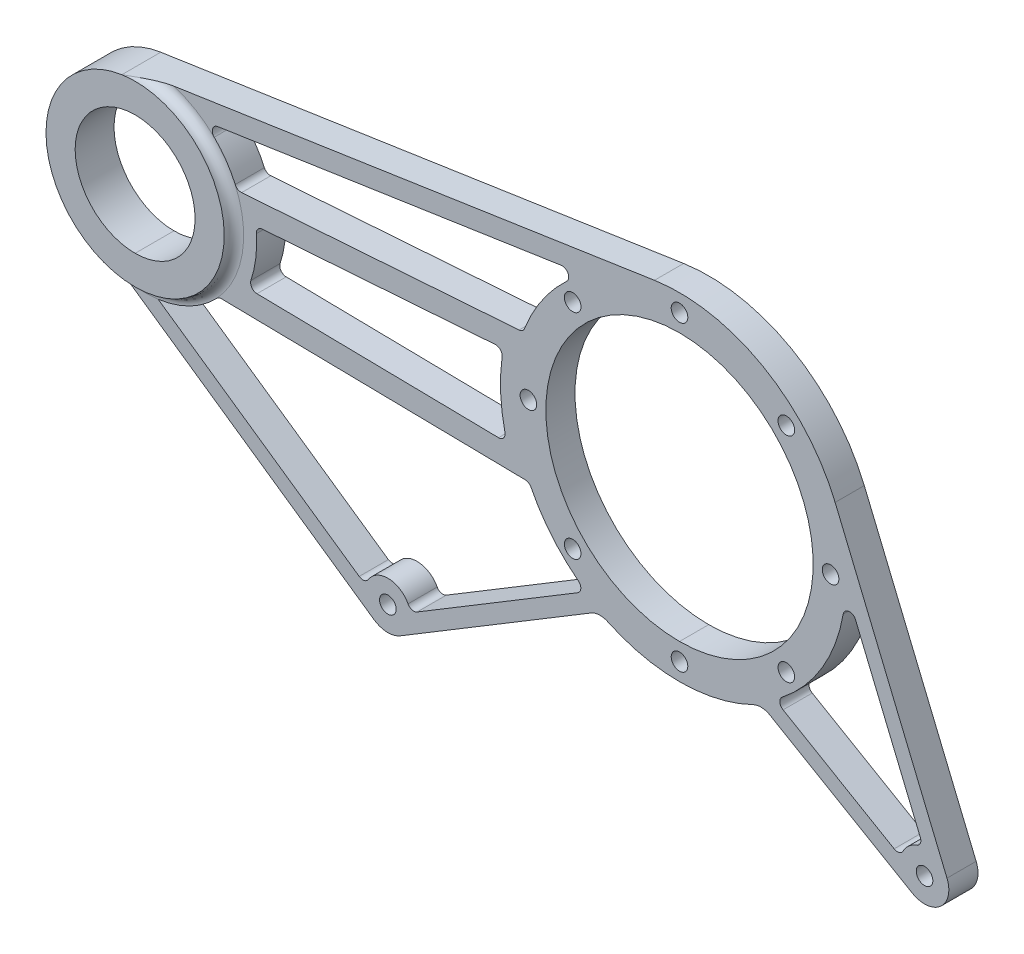
SolidWorks part; units mm, degrees
note: '?' marks a value the reader was unsure of.
material "6061-T6 (SS)"
ref_plane "Front Plane" through (0, 0, 0) normal (0, 0, 1) x (1, 0, 0)
ref_plane "Top Plane" through (0, 0, 0) normal (0, 1, 0) x (1, 0, 0)
ref_plane "Right Plane" through (0, 0, 0) normal (1, 0, 0) x (0, 0, -1)
sketch "Sketch1" plane through (0, 0, 0) normal (0, 0, 1) x (1, 0, 0)
  line L0 (-329.0358, 136.1378) -> (-124.1059, 166.9079)
  line L1 (-343.7594, 72.9056) -> (-234.0298, -3.2296)
  line L2 (-223.6766, -3.5577) -> (-149.0272, 41.5159)
  line L3 (-114.3, 88.9) -> (-114.3, 101.6) construction
  line L4 (-53.3056, 126.9173) -> (-9.4675, 21.3025)
  line L5 (-23.0618, 9.4221) -> (-78.8665, 41.9532)
  circle A0 centre (-114.3, 88.9) radius 82.9716 construction
  circle A1 centre (-228.6, -20.8038) radius 12.7 construction
  circle A2 centre (0, 0) radius 12.7 construction
  circle A3 centre (-323.85, 101.6) radius 114 construction
  circle A4 centre (-323.85, 101.6) radius 23.5
  circle A5 centre (-114.3, 101.6) radius 52.3875
  arc A6 (-142.4404, 41.8555) -> (-85.4371, 42.2012) centre (-114.3, 101.6) ccw
  circle A7 centre (-323.85, 101.6) radius 34.925
  arc A8 (-223.6766, -3.5577) -> (-234.0298, -3.2296) centre (-228.6, 4.5962) cw
  arc A9 (-9.4675, 21.3025) -> (-23.0618, 9.4221) centre (-18.2648, 17.651) cw
  circle A10 centre (-228.6, 4.5962) radius 3.2512
  circle A11 centre (-18.2648, 17.651) radius 3.2512
  arc A12 (-142.4404, 41.8555) -> (-149.0272, 41.5159) centre (-145.4168, 35.5364) ccw
  arc A13 (-78.8665, 41.9532) -> (-85.4371, 42.2012) centre (-82.3843, 35.9187) ccw
  circle A14 centre (-114.3, 101.6) radius 66.04 construction
  arc A15 (-124.1059, 166.9079) -> (-53.3056, 126.9173) centre (-114.3, 101.6) cw
  dimension "D1" = 88.9
  dimension "D2" = 12.7
  dimension "D3" = 25.4
  dimension "D4" = 25.4
  dimension "D8" = 165.9433
  dimension "D9" = 228
  dimension "D10" = 47
  dimension "D12" = 104.775
  dimension "D14" = 132.08
  dimension "D15" = 69.85
  dimension "D16" = 9.525
  dimension "D18" = 9.525
  dimension "D20" = 6.5024
  dimension "D21" = 6.5024
  dimension "D23" = 6.985
  dimension "D24" = 6.985
  dimension "D25" = 66.04
  dimension "D5" = 228.6
  dimension "D6" = 20.8038
  dimension "D7" = 114.3
  dimension "D11" = 12.7
  dimension "D13" = 209.55
  dimension "D17" = 25.4
  dimension "D19" = 25.4
  dimension "D22" = 17.651
extrude "Boss-Extrude1" add sketch "Sketch1" along normal blind 11.43 contours A7 A4 | A8 L2 A6 L0 A7 L1 A10 | A6 A5 | A9 L4 A6 L5 A11
ref_point "Point4"
sketch "Sketch5" plane through (0, 0, 11.43) normal (0, 0, 1) x (1, 0, 0)
  circle A0 centre (-323.85, 101.6) radius 23.5
  circle A1 centre (-323.85, 101.6) radius 34.925
sketch "Sketch8" plane through (0, 0, 11.43) normal (0, 0, 1) x (1, 0, 0)
  line L0 (-114.3, 101.6) -> (-114.3, 160.8137) construction
  circle A0 centre (-114.3, 101.6) radius 59.2137 construction
  circle A1 centre (-114.3, 160.8137) radius 3.2512
  circle A2 centre (-72.4296, 143.4704) radius 3.2512
  circle A3 centre (-55.0862, 101.6) radius 3.2512
  circle A4 centre (-72.4296, 59.7296) radius 3.2512
  circle A5 centre (-114.3, 42.3863) radius 3.2512
  circle A6 centre (-156.1704, 59.7296) radius 3.2512
  circle A7 centre (-173.5137, 101.6) radius 3.2512
  circle A8 centre (-156.1704, 143.4704) radius 3.2512
  point P22 (-114.3, 101.6)
  dimension "D1" = 118.4275
  dimension "D2" = 6.5024
  dimension "D3" = 8
extrude "Cut-Extrude3" cut sketch "Sketch8" against normal through all both and the other way through all
sketch "Sketch9" plane through (0, 0, 0) normal (0, 0, -1) x (-1, 0, 0)
  line L0 (45.3091, 91.088) -> (19.9022, 29.8777)
  line L1 (30.1621, 20.9113) -> (73.7102, 46.2975)
  line L2 (160.643, 153.7165) -> (300.7346, 132.6818)
  line L3 (154.2026, 45.8088) -> (217.1378, 7.8082)
  line L4 (239.8358, 8.5276) -> (318.6539, 63.2151)
  line L8 (23.0618, 9.4221) -> (78.8665, 41.9532) construction
  line L9 (53.3056, 126.9173) -> (9.4675, 21.3025) construction
  line L10 (223.6766, -3.5577) -> (149.0272, 41.5159) construction
  line L11 (343.7594, 72.9056) -> (234.0298, -3.2296) construction
  line L12 (329.0358, 136.1378) -> (124.1059, 166.9079) construction
  line L15 (175.5506, 123.6169) -> (287.7463, 115.633)
  line L20 (173.1667, 73.8315) -> (294.9509, 75.8077)
  line L23 (183.336, 114.1504) -> (280.3999, 107.2433)
  line L24 (181.92, 82.8647) -> (283.5041, 84.5131)
  arc A0 (50.1581, 90.5457) -> (74.0036, 50.4866) centre (114.3, 101.6) ccw
  arc A1 (158.5394, 149.3416) -> (175.5506, 123.6169) centre (114.3, 101.6) cw
  arc A3 (318.6539, 63.2151) -> (294.9509, 75.8077) centre (323.85, 101.6) cw
  circle A4 centre (114.3, 101.6) radius 52.3875 construction
  arc A9 (158.5394, 149.3416) -> (160.643, 153.7165) centre (160.2658, 151.2047) cw
  arc A11 (74.0036, 50.4866) -> (73.7102, 46.2975) centre (72.431, 48.4919) cw
  arc A12 (50.1581, 90.5457) -> (45.3091, 91.088) centre (47.655, 90.1143) ccw
  arc A13 (236.2241, 9.2841) -> (220.6943, 8.7919) centre (228.6, 4.5962) ccw
  arc A14 (26.6236, 21.945) -> (21.4006, 26.5096) centre (18.2648, 17.651) ccw
  arc A16 (154.2026, 45.8088) -> (153.9675, 49.997) centre (155.5155, 47.9832) cw
  arc A17 (239.8358, 8.5276) -> (236.2241, 9.2841) centre (238.3878, 10.6145) cw
  arc A18 (217.1378, 7.8082) -> (220.6943, 8.7919) centre (218.4507, 9.9826) ccw
  arc A19 (30.1621, 20.9113) -> (26.6236, 21.945) centre (28.8829, 23.1057) cw
  arc A20 (19.9022, 29.8777) -> (21.4006, 26.5096) centre (22.2481, 28.904) ccw
  arc A30 (287.7463, 115.633) -> (300.7346, 132.6818) centre (323.85, 101.6) cw
  circle A32 centre (323.85, 101.6) radius 34.925 construction
  arc A37 (173.1667, 73.8315) -> (153.9675, 49.997) centre (114.3, 101.6) cw
  arc A40 (280.3999, 107.2433) -> (283.5041, 84.5131) centre (323.85, 101.6) ccw
  circle A41 centre (323.85, 101.6) radius 34.925 construction
  circle A42 centre (323.85, 101.6) radius 23.5 construction
  arc A44 (183.336, 114.1504) -> (181.92, 82.8647) centre (114.3, 101.6) cw
  dimension "D8" = 17.9001
  dimension "D9" = 9.3972
  dimension "D1" = 6.35
  dimension "D2" = 6.35
  dimension "D4" = 6.35
  dimension "D5" = 7.62
  dimension "D10" = 12.7
  dimension "D6" = 12.7
  dimension "D3" = 6.35
  dimension "D14" = 8.89
  dimension "D7" = 17.78
  dimension "D12" = 8.89
  dimension "D13" = 3.81
  dimension "D11" = 8.89
  dimension "D15" = 5
extrude "Cut-Extrude4" cut sketch "Sketch9" against normal through all
sketch "Sketch10" plane through (0, 0, 11.43) normal (0, 0, 1) x (1, 0, 0)
  circle A0 centre (-323.85, 101.6) radius 23.5 construction
  circle A1 centre (-323.85, 101.6) radius 34.925 construction
  circle A2 centre (-323.85, 101.6) radius 23.5
  circle A3 centre (-323.85, 101.6) radius 34.925
extrude "Boss-Extrude2" add sketch "Sketch10" along normal blind 3.81
fillet "Fillet3" radius 3.81 1 edges at (-289.835, 93.6796, 11.43)
fillet "Fillet5" radius 2.54 9 edges at (-173.1667, 73.8315, 5.715) (-181.92, 82.8647, 5.715) (-183.336, 114.1504, 5.715) (-175.5506, 123.6169, 5.715) (-294.9509, 75.8077, 5.715) (-283.5041, 84.5131, 5.715) (-280.3999, 107.2433, 5.715) (-287.7463, 115.633, 5.715) (-300.7346, 132.6818, 5.715)
ref_axis "Axis1" through (-114.3, 101.6, 11.43) along (0, 0, -1)?
ref_plane "Plane1" through (-114.3, 0, 0) normal (1, 0, 0) x (0, 0, -1)
ref_plane "Plane2" through (-323.85, 0, 0) normal (1, 0, 0) x (0, 0, -1)
split line "Split Line2"
split line "Split Line1"
equation "\"Base Width\"=0.5"
equation "\"D10@Sketch9\"=\"Base Width\""
equation "\"D6@Sketch9\"=\"Base Width\""
